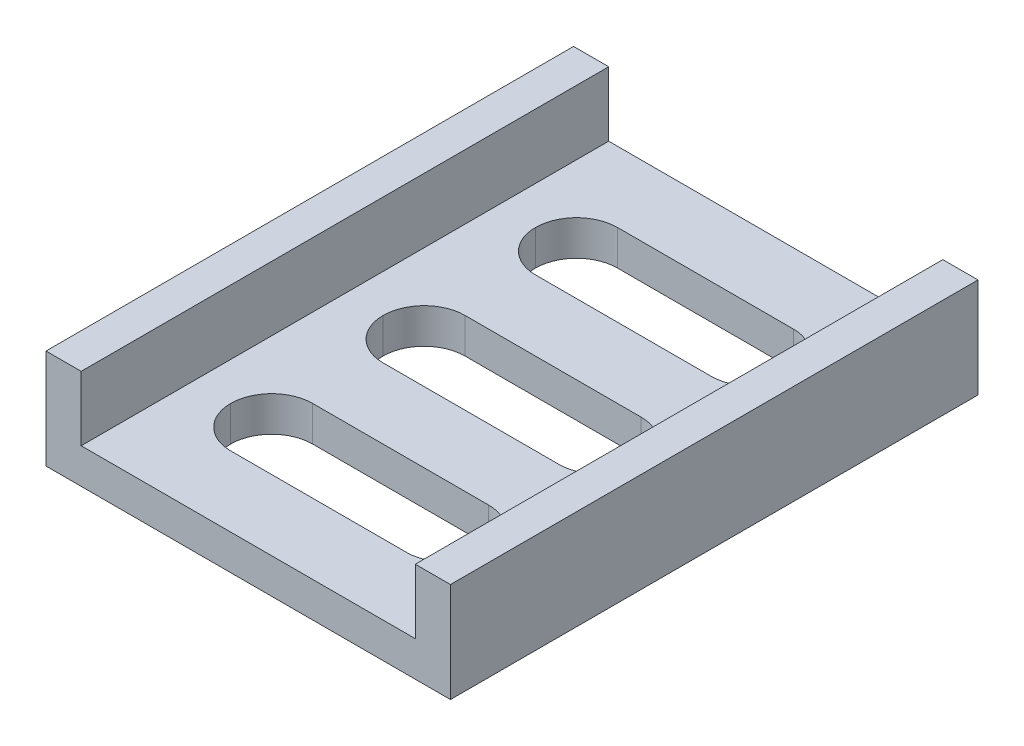
SolidWorks part; units mm, degrees
material "Custom Plastic"
ref_plane "Front Plane" through (0, 0, 0) normal (0, 0, 1) x (1, 0, 0)
ref_plane "Top Plane" through (0, 0, 0) normal (0, 1, 0) x (1, 0, 0)
ref_plane "Right Plane" through (0, 0, 0) normal (1, 0, 0) x (0, 0, -1)
sketch "Sketch2" plane through (0, 0, 0) normal (0, 1, 0) x (1, 0, 0)
  line L1 (-17.25, -22.5) -> (17.25, -22.5)
  line L2 (-17.25, -22.5) -> (-17.25, 22.5)
  line L3 (-17.25, 22.5) -> (17.25, 22.5)
  line L4 (17.25, -22.5) -> (17.25, 22.5)
  line L5 (-17.25, -22.5) -> (17.25, 22.5) construction
  line L6 (-17.25, 22.5) -> (17.25, -22.5) construction
  point P0 (0, 0)
  dimension "D1" = 34.5
  dimension "D2" = 45
extrude "Boss-Extrude1" add sketch "Sketch2" along normal blind 3
sketch "Sketch3" plane through (0, 3, 0) normal (0, 1, 0) x (1, 0, 0)
  line L0 (-14.25, 22.5) -> (-14.25, -22.5)
  line L1 (17.25, 22.5) -> (-17.25, 22.5) construction
  line L2 (-17.25, -22.5) -> (17.25, -22.5) construction
  line L3 (14.25, 22.5) -> (14.25, -22.5)
  line L4 (17.25, -22.5) -> (17.25, 22.5) construction
  line L5 (-17.25, 22.5) -> (-17.25, -22.5) construction
  line L6 (-14.25, 22.5) -> (-17.25, 22.5)
  line L7 (-17.25, 22.5) -> (-17.25, -22.5)
  line L8 (-17.25, -22.5) -> (-14.25, -22.5)
  line L9 (14.25, 22.5) -> (17.25, 22.5)
  line L10 (17.25, 22.5) -> (17.25, -22.5)
  line L11 (17.25, -22.5) -> (14.25, -22.5)
  dimension "D1" = 3
  dimension "D2" = 3
extrude "Boss-Extrude2" add sketch "Sketch3" along normal blind 5.5
sketch "Sketch4" plane through (0, 0, 0) normal (0, -1, 0) x (1, 0, 0)
  line L0 (-39.5265, 0) -> (35.5876, 0) construction
  line L2 (-39.5265, 13) -> (35.5876, 13) construction
  line L3 (-39.5265, -13) -> (42.0254, -13) construction
  line L4 (-11, 9.5) -> (11, 9.5)
  line L5 (-11, 9.5) -> (-11, 16.5)
  line L6 (-11, 16.5) -> (11, 16.5)
  line L7 (11, 9.5) -> (11, 16.5)
  line L8 (-11, 9.5) -> (11, 16.5) construction
  line L9 (-11, 16.5) -> (11, 9.5) construction
  line L10 (-11, -3.5) -> (11, -3.5)
  line L11 (-11, -3.5) -> (-11, 3.5)
  line L12 (-11, 3.5) -> (11, 3.5)
  line L13 (11, -3.5) -> (11, 3.5)
  line L14 (-11, -3.5) -> (11, 3.5) construction
  line L15 (-11, 3.5) -> (11, -3.5) construction
  line L16 (42.0254, -13) -> (0.6294, -13) construction
  line L17 (0, 29.2934) -> (0, -40.1208) construction
  line L19 (-11, -16.5) -> (11, -16.5)
  line L20 (-11, -16.5) -> (-11, -9.5)
  line L21 (-11, -9.5) -> (11, -9.5)
  line L22 (11, -16.5) -> (11, -9.5)
  line L23 (-11, -16.5) -> (11, -9.5) construction
  line L24 (-11, -9.5) -> (11, -16.5) construction
  point P3 (0, 13)
  point P4 (0, 13)
  point P11 (0, 0)
  point P21 (0, -13)
  point P22 (0, -13)
  dimension "D1" = 13
  dimension "D2" = 13
  dimension "D3" = 7
  dimension "D4" = 7
  dimension "D5" = 7
  dimension "D6" = 22
  dimension "D7" = 22
  dimension "D8" = 22
extrude "Cut-Extrude1" cut sketch "Sketch4" against normal blind 8
fillet "Fillet1" radius 3.5 12 edges at (-11, 1.5, -9.5) (-11, 1.5, -16.5) (11, 1.5, -9.5) (11, 1.5, -16.5) (11, 1.5, -3.5) (-11, 1.5, -3.5) (-11, 1.5, 3.5) (11, 1.5, 3.5) (11, 1.5, 9.5) (11, 1.5, 16.5) (-11, 1.5, 9.5) (-11, 1.5, 16.5)
